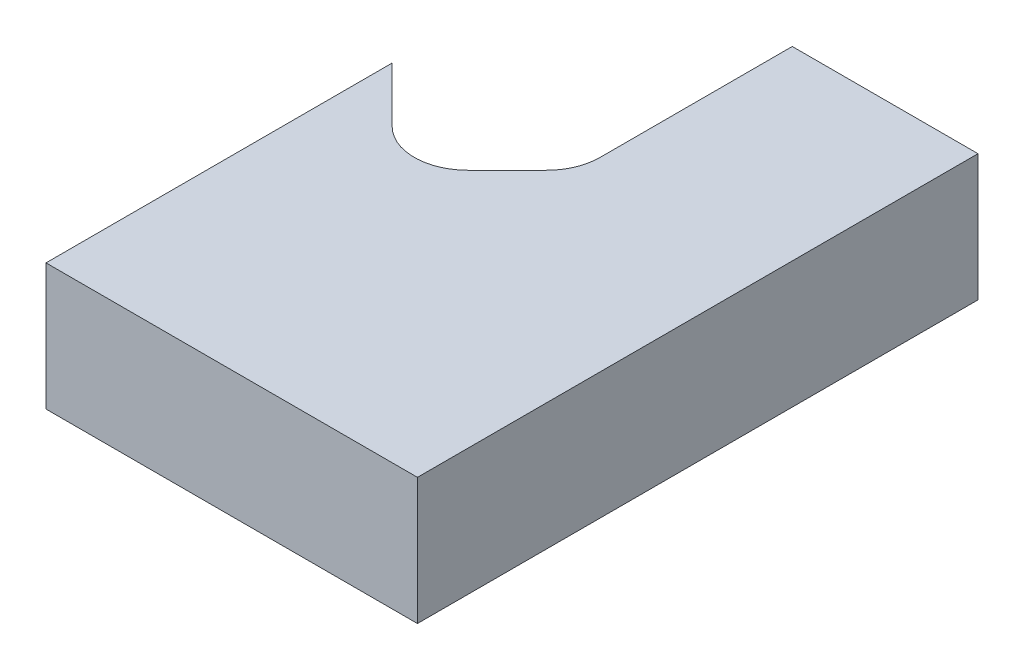
SolidWorks part; units mm, degrees
material "6061 Alloy"
ref_plane "Front" through (0, 0, 0) normal (0, 0, 1) x (1, 0, 0)
ref_plane "Top" through (0, 0, 0) normal (0, 1, 0) x (1, 0, 0)
ref_plane "Right" through (0, 0, 0) normal (1, 0, 0) x (0, 0, -1)
sketch "Sketch1" plane through (0, 0, 0) normal (0, 1, 0) x (1, 0, 0)
  line L0 (0, 0) -> (0, 41)
  line L1 (0, -50) -> (0, 50) construction
  line L4 (44, 41) -> (44, 0)
  line L5 (44, 0) -> (0, 0)
  line L6 (0, 41) -> (11, 30)
  line L7 (11, 30) -> (22, 41)
  line L8 (22, 41) -> (22, 66.4)
  line L9 (22, 66.4) -> (44, 66.4)
  line L10 (44, 66.4) -> (44, 41)
  point P11 (0, 0)
  dimension "D1" = 44
  dimension "D2" = 22
  dimension "D3" = 25.4
  dimension "D4" = 41
extrude "Boss-Extrude1" add sketch "Sketch1" along normal blind 15
ref_plane "Plane1" through (0, 0, -12.7) normal (0, 0, -1) x (-1, 0, 0)
hole_wizard "M4 Clearance Hole5" positions "Sketch10" profile "Sketch11" hole size "M4" standard "ANSI Metric" end condition through all
sketch "Sketch10" plane through (0, 0, -12.7) normal (0, 0, -1) x (-1, 0, 0)
  line L0 (-4.5, 15) -> (-4.5, 0) construction
  line L2 (50, 0) -> (-50, 0) construction
  line L5 (-39.5, 15) -> (-39.5, 0) construction
  line L8 (-39.5, 7.5) -> (-44, 7.5) construction
  line L11 (-4.5, 7.5) -> (0, 7.5) construction
  line L12 (0, 50) -> (0, -50) construction
  line L13 (-44, 15) -> (-44, 0) construction
  line L15 (-44, 15) -> (-22, 15) construction
  line L16 (-11, 15) -> (0, 15) construction
  point P0 (-39.5, 7.5)
  point P2 (-4.5, 7.5)
  point P36 (0, 0)
  point P37 (0, 0)
  point P38 (0, 0)
  point P39 (0, 0)
  point P40 (0, 0)
  point P41 (0, 0)
  point P42 (0, 0)
  point P45 (0, 0)
  point P48 (0, 0)
  point P49 (0, 0)
  dimension "D1" = 35
sketch "Sketch11" plane through (39.5, 7.5, -12.7) normal (1, 0, 0) x (0, -1, 0)
  line L0 (0, 0) -> (0, 53.7)
  line L1 (0, 53.7) -> (2.25, 53.7)
  line L2 (2.25, 53.7) -> (2.25, 0)
  line L5 (2.25, 0) -> (0, 0)
  line L11 (0, -6.35) -> (0, 107.95) construction
  dimension "Thru Hole Dia." = 4.5
  dimension "Thru Hole Depth" = 53.7
hole_wizard "Ø6.0mm Dowel Hole1" positions "Sketch12" profile "Sketch13" hole size "Ø6.0" standard "ANSI Metric" end condition through all
sketch "Sketch12" plane through (0, 0, -12.7) normal (0, 0, -1) x (-1, 0, 0)
  line L0 (-44, 7.5) -> (-39.5, 7.5) construction
  line L3 (0, 7.5) -> (-4.5, 7.5) construction
  line L4 (0, 50) -> (0, -50) construction
  line L5 (-44, 15) -> (-44, 0) construction
  point P0 (-39.5, 7.5)
  point P2 (-4.5, 7.5)
  point P15 (0, 0)
  point P16 (0, 0)
  dimension "D1" = 35
sketch "Sketch13" plane through (39.5, 7.5, -12.7) normal (1, 0, 0) x (0, -1, 0)
  line L0 (0, 0) -> (0, 53.7)
  line L1 (0, 53.7) -> (3.75, 53.7)
  line L2 (3.75, 53.7) -> (3.75, 0)
  line L5 (3.75, 0) -> (0, 0)
  line L11 (0, -6.35) -> (0, 107.95) construction
  dimension "Thru Hole Dia." = 7.5
  dimension "Thru Hole Depth" = 53.7
fillet "Fillet1" radius 6.35 2 edges at (11, 7.5, -30) (22, 7.5, -41)
